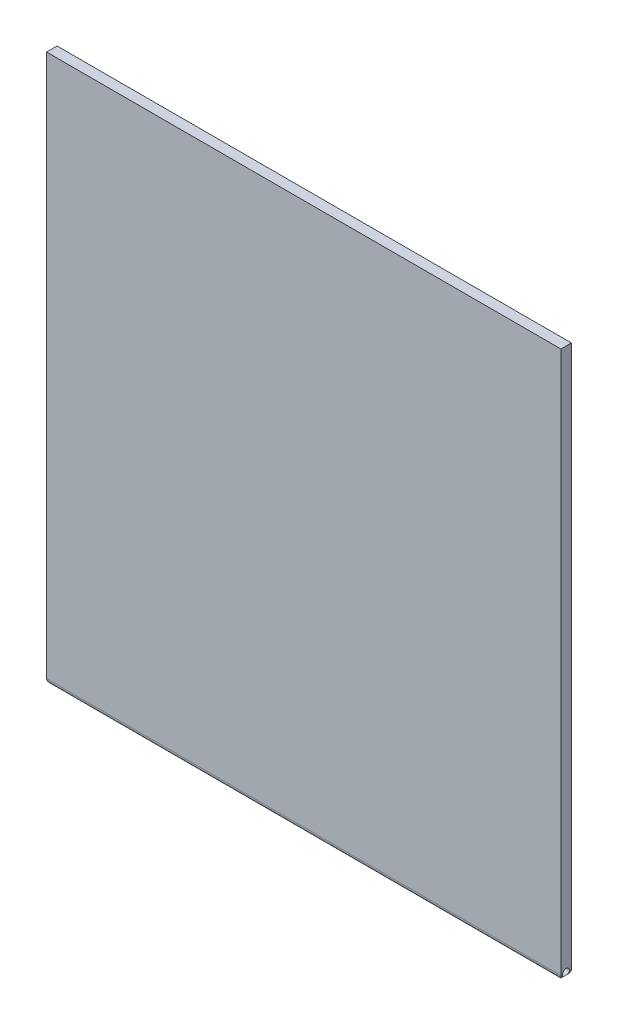
SolidWorks part; units mm, degrees
material "S-玻璃纤维"
ref_plane "前视基准面" through (0, 0, 0) normal (0, 0, 1) x (1, 0, 0)
ref_plane "上视基准面" through (0, 0, 0) normal (0, 1, 0) x (1, 0, 0)
ref_plane "右视基准面" through (0, 0, 0) normal (1, 0, 0) x (0, 0, -1)
sketch "草图1" plane through (0, 0, 0) normal (0, 0, 1) x (1, 0, 0)
  line L1 (-108.7978, 111.4116) -> (38.5022, 111.4116)
  line L2 (-108.7978, 111.4116) -> (-108.7978, -45.4884)
  line L3 (-108.7978, -45.4884) -> (38.5022, -45.4884)
  line L4 (38.5022, 111.4116) -> (38.5022, -45.4884)
  line L5 (-108.7978, 111.4116) -> (38.5022, -45.4884) construction
  line L6 (-108.7978, -45.4884) -> (38.5022, 111.4116) construction
  point P0 (-35.1478, 32.9616)
  dimension "D1" = 156.9
  dimension "D2" = 147.3
extrude "凸台-拉伸1" add sketch "草图1" along normal blind 3
sketch "草图2" plane through (38.5022, 0, 0) normal (1, 0, 0) x (0, 0, -1)
  circle A0 centre (-1.5, -43.9884) radius 1
  dimension "D2" = 2
extrude "切除-拉伸1" cut sketch "草图2" against normal through all
fillet "圆角1" radius 1.5 4 edges at (-108.7978, -45.4884, 1.5) (-35.1478, -45.4884, 3) (38.5022, -45.4884, 1.5) (-35.1478, -45.4884, 0)
